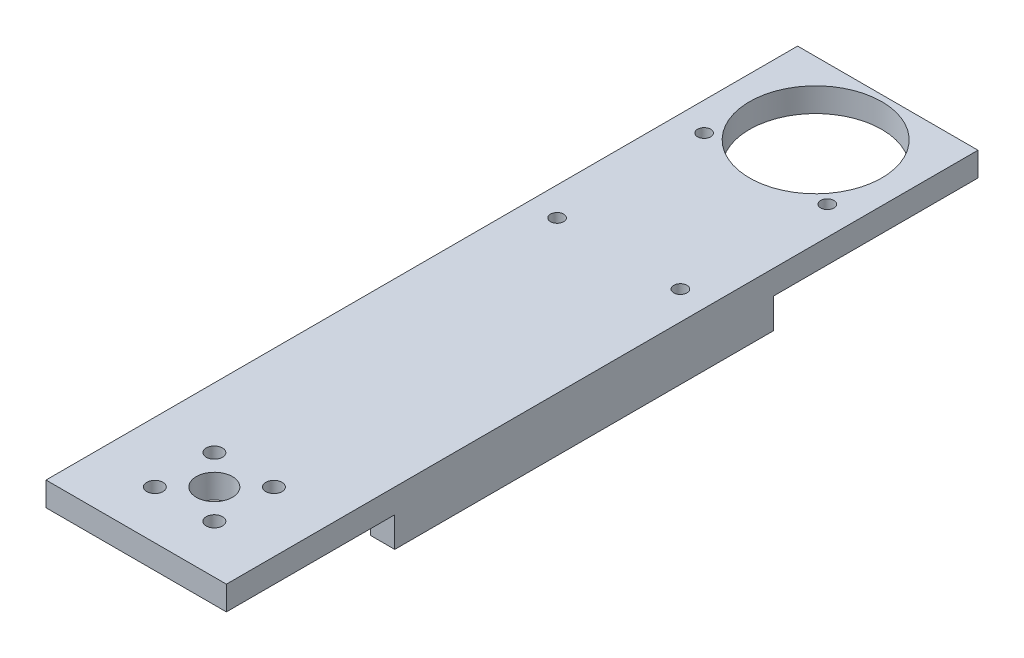
SolidWorks part; units mm, degrees
ref_plane "Front Plane" through (0, 0, 0) normal (0, 0, 1) x (1, 0, 0)
ref_plane "Top Plane" through (0, 0, 0) normal (0, 1, 0) x (1, 0, 0)
ref_plane "Right Plane" through (0, 0, 0) normal (1, 0, 0) x (0, 0, -1)
ref_plane "PZ_m112_000" through (0, 0, -112) normal (0, 0, 1) x (1, 0, 0)
sketch "S_box1" plane through (0, 0, -112) normal (0, 0, 1) x (1, 0, 0)
  line L0 (-15, -20) -> (15, -20)
  line L1 (15, -20) -> (15, -16)
  line L2 (15, -16) -> (-15, -16)
  line L3 (-15, -16) -> (-15, -20)
  dimension "P1" = 15
  dimension "P2" = 20
  dimension "P3" = 15
  dimension "P4" = 20
  dimension "P5" = 15
  dimension "P6" = 16
  dimension "P7" = 15
  dimension "P8" = 16
extrude "Boss_1" add sketch "S_box1" along normal blind 125
ref_plane "PZ_m78_000" through (0, 0, -78) normal (0, 0, 1) x (1, 0, 0)
sketch "S_box2" plane through (0, 0, -78) normal (0, 0, 1) x (1, 0, 0)
  line L0 (-15, -25) -> (-11, -25)
  line L1 (-11, -25) -> (-11, -19.5)
  line L2 (-11, -19.5) -> (-15, -19.5)
  line L3 (-15, -19.5) -> (-15, -25)
  dimension "P1" = 15
  dimension "P2" = 25
  dimension "P3" = 11
  dimension "P4" = 25
  dimension "P5" = 11
  dimension "P6" = 19.5
  dimension "P7" = 15
  dimension "P8" = 19.5
extrude "Boss_2" add sketch "S_box2" along normal blind 63
sketch "S_box3" plane through (0, 0, -78) normal (0, 0, 1) x (1, 0, 0)
  line L0 (11, -25) -> (15, -25)
  line L1 (15, -25) -> (15, -19.5)
  line L2 (15, -19.5) -> (11, -19.5)
  line L3 (11, -19.5) -> (11, -25)
  dimension "P1" = 11
  dimension "P2" = 25
  dimension "P3" = 15
  dimension "P4" = 25
  dimension "P5" = 15
  dimension "P6" = 19.5
  dimension "P7" = 11
  dimension "P8" = 19.5
extrude "Boss_3" add sketch "S_box3" along normal blind 63
ref_plane "PY_m20_100" through (0, -20.1, 0) normal (0, 1, 0) x (1, 0, 0)
sketch "S_hole4" plane through (0, -20.1, 0) normal (0, 1, 0) x (1, 0, 0)
  circle A0 centre (0, 0) radius 3
  dimension "D1_S_hole4" = 6
extrude "Hole_4" cut sketch "S_hole4" along normal blind 4.2
sketch "S_hole5" plane through (0, -20.1, 0) normal (0, 1, 0) x (1, 0, 0)
  circle A0 centre (4.9497, -4.9497) radius 1.35
  dimension "D1_S_hole5" = 2.7
  dimension "P2" = 4.9497
  dimension "P3" = 4.9497
extrude "Hole_5" cut sketch "S_hole5" along normal blind 4.2
sketch "S_hole6" plane through (0, -20.1, 0) normal (0, 1, 0) x (1, 0, 0)
  circle A0 centre (-4.9497, -4.9497) radius 1.35
  dimension "D1_S_hole6" = 2.7
  dimension "P2" = 4.9497
  dimension "P3" = 4.9497
extrude "Hole_6" cut sketch "S_hole6" along normal blind 4.2
sketch "S_hole7" plane through (0, -20.1, 0) normal (0, 1, 0) x (1, 0, 0)
  circle A0 centre (-4.9497, 4.9497) radius 1.35
  dimension "D1_S_hole7" = 2.7
  dimension "P2" = 4.9497
  dimension "P3" = 4.9497
extrude "Hole_7" cut sketch "S_hole7" along normal blind 4.2
sketch "S_hole8" plane through (0, -20.1, 0) normal (0, 1, 0) x (1, 0, 0)
  circle A0 centre (4.9497, 4.9497) radius 1.35
  dimension "D1_S_hole8" = 2.7
  dimension "P2" = 4.9497
  dimension "P3" = 4.9497
extrude "Hole_8" cut sketch "S_hole8" along normal blind 4.2
sketch "S_hole9" plane through (0, -20.1, 0) normal (0, 1, 0) x (1, 0, 0)
  circle A0 centre (0, 100) radius 11
  dimension "D1_S_hole9" = 22
  dimension "P2" = 100
extrude "Hole_9" cut sketch "S_hole9" along normal blind 4.2
sketch "S_hole10" plane through (0, -20.1, 0) normal (0, 1, 0) x (1, 0, 0)
  circle A0 centre (-10.25, 91.7) radius 1.1
  dimension "D1_S_hole10" = 2.2
  dimension "P2" = 10.25
  dimension "P3" = 91.7
extrude "Hole_10" cut sketch "S_hole10" along normal blind 4.2
sketch "S_hole11" plane through (0, -20.1, 0) normal (0, 1, 0) x (1, 0, 0)
  circle A0 centre (10.25, 91.7) radius 1.1
  dimension "D1_S_hole11" = 2.2
  dimension "P2" = 10.25
  dimension "P3" = 91.7
extrude "Hole_11" cut sketch "S_hole11" along normal blind 4.2
sketch "S_hole12" plane through (0, -20.1, 0) normal (0, 1, 0) x (1, 0, 0)
  circle A0 centre (-10.25, 67.25) radius 1.1
  dimension "D1_S_hole12" = 2.2
  dimension "P2" = 10.25
  dimension "P3" = 67.25
extrude "Hole_12" cut sketch "S_hole12" along normal blind 4.2
sketch "S_hole13" plane through (0, -20.1, 0) normal (0, 1, 0) x (1, 0, 0)
  circle A0 centre (10.25, 67.25) radius 1.1
  dimension "D1_S_hole13" = 2.2
  dimension "P2" = 10.25
  dimension "P3" = 67.25
extrude "Hole_13" cut sketch "S_hole13" along normal blind 4.2
equation "\"plate_t\" = 3"
equation "\"clearance\" = 0.4"
